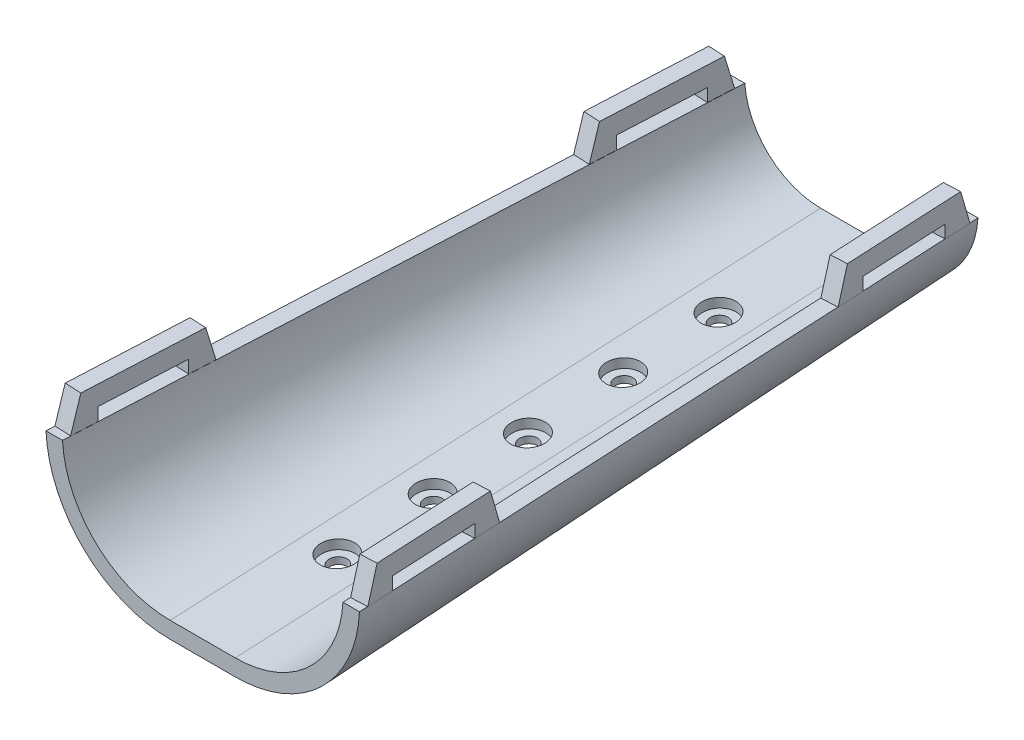
SolidWorks part; units mm, degrees
ref_plane "Front Plane" through (0, 0, 0) normal (0, 0, 1) x (1, 0, 0)
ref_plane "Top Plane" through (0, 0, 0) normal (0, 1, 0) x (1, 0, 0)
ref_plane "Right Plane" through (0, 0, 0) normal (1, 0, 0) x (0, 0, -1)
sketch "Sketch1" plane through (0, 0, 0) normal (0, 0, 1) x (1, 0, 0)
  line L0 (-7.5, 0) -> (7.5, 0)
  line L1 (-28.8, 20) -> (28.8, 20)
  line L3 (-7.5, 3.8) -> (7.5, 3.8)
  line L4 (-24.2716, 16.2) -> (24.2716, 16.2) construction
  arc A0 (7.5, 0) -> (28.8, 20) centre (7.5, 21.3423) ccw
  arc A1 (-7.5, 0) -> (-28.8, 20) centre (-7.5, 21.3423) cw
  arc A2 (7.5, 3.8) -> (24.2716, 16.2) centre (7.5, 21.3423) ccw
  arc A3 (-7.5, 3.8) -> (-24.2716, 16.2) centre (-7.5, 21.3423) cw
  arc A4 (24.2716, 16.2) -> (24.9908, 20) centre (7.5, 21.3423) ccw
  arc A5 (-24.2716, 16.2) -> (-24.9908, 20) centre (-7.5, 21.3422) cw
  point P6 (0, 0)
  dimension "D3" = 3.8
  dimension "D1" = 15
  dimension "D2" = 57.6
  dimension "D4" = 20
extrude "Boss-Extrude1" add sketch "Sketch1" along normal blind 150 draft 2.8 contours L4 A3 L3 A2 | A5 L4 A4 L1 | A3 A5 L1 A1 L0 A0 A4 A2 L3 region at (-21.6916, 6.2282, 0) region at (0, 18.1092, 0) region at (0, 10.6529, 0) draft outward yes
extrude "Cut-Extrude1" cut sketch "Sketch1<3>" along normal through all draft 2.8 contours L4 A3 L3 A2 | A5 L4 A4 L1 region at (0, 18.1092, 0) region at (0, 10.6529, 0) draft outward yes
sketch "Sketch1<3>" plane through (0, 0, 0) normal (0, 0, 1) x (1, 0, 0) same geometry as "Sketch1"
sketch "Sketch4" plane through (0, 0, 0) normal (0, 0, -1) x (-1, 0, 0)
  line L0 (43.2855, 20) -> (-43.2855, 20)
  line L1 (-43.2855, 20) -> (-43.2855, 37.75)
  line L2 (-43.2855, 37.75) -> (43.2855, 37.75)
  line L3 (43.2855, 37.75) -> (43.2855, 20)
  point P4 (0, 20)
  dimension "D1" = 17.75
  dimension "D2" = 86.571
extrude "Cut-Extrude2" cut sketch "Sketch4" against normal through all
ref_plane "Plane1" through (28.7734, 0, -1.4073) normal (0.9988, 0, -0.0488) x (-0.0488, 0, -0.9988)
sketch "Sketch5" plane through (28.7734, 0, -1.4073) normal (0.9988, 0, -0.0488) x (-0.0488, 0, -0.9988)
  line L0 (-149.5867, 20) -> (-147.3367, 27.5)
  line L1 (-1.4069, 20) -> (-151.5867, 20) construction
  line L2 (-147.3367, 27.5) -> (-119.8367, 27.5)
  line L3 (-119.8367, 27.5) -> (-117.5867, 20)
  line L4 (-117.5867, 20) -> (-123.5867, 20)
  line L5 (-123.5867, 20) -> (-123.5867, 23)
  line L6 (-123.5867, 23) -> (-143.5867, 23)
  line L7 (-143.5867, 23) -> (-143.5867, 20)
  line L8 (-143.5867, 20) -> (-149.5867, 20)
  line L9 (-76.4968, 20) -> (-76.4968, 42.8305) construction
  line L10 (-9.4069, 23) -> (-9.4069, 20)
  line L11 (-29.4069, 23) -> (-9.4069, 23)
  line L12 (-29.4069, 20) -> (-29.4069, 23)
  line L13 (-35.4069, 20) -> (-29.4069, 20)
  line L14 (-33.1569, 27.5) -> (-35.4069, 20)
  line L15 (-5.6569, 27.5) -> (-33.1569, 27.5)
  line L16 (-3.4069, 20) -> (-5.6569, 27.5)
  line L17 (-9.4069, 20) -> (-3.4069, 20)
  point P13 (-133.5867, 23)
  point P14 (-133.5867, 27.5)
  dimension "D1" = 20
  dimension "D2" = 27.5
  dimension "D3" = 6
  dimension "D4" = 7.5
  dimension "D5" = 4.5
  dimension "D6" = 2
  dimension "D7" = 41.0899
extrude "Boss-Extrude2" add sketch "Sketch5" against normal blind 3.8
ref_plane "Plane2" through (-28.7734, 0, -1.4073) normal (-0.9988, 0, -0.0488) x (-0.0488, 0, 0.9988)
sketch "Sketch6" plane through (-28.7734, 0, -1.4073) normal (-0.9988, 0, -0.0488) x (-0.0488, 0, 0.9988)
  line L0 (149.5867, 20) -> (147.3367, 27.5)
  line L1 (147.3367, 27.5) -> (119.8367, 27.5)
  line L2 (119.8367, 27.5) -> (117.5867, 20)
  line L3 (117.5867, 20) -> (123.5867, 20)
  line L4 (123.5867, 20) -> (123.5867, 23)
  line L5 (123.5867, 23) -> (143.5867, 23)
  line L6 (143.5867, 23) -> (143.5867, 20)
  line L9 (143.5867, 20) -> (149.5867, 20)
  line L10 (151.5867, 20) -> (1.4069, 20) construction
  line L11 (76.4968, 20.9106) -> (76.4968, 45.7077) construction
  line L12 (9.4069, 23) -> (9.4069, 20)
  line L13 (29.4069, 23) -> (9.4069, 23)
  line L14 (29.4069, 20) -> (29.4069, 23)
  line L15 (35.4069, 20) -> (29.4069, 20)
  line L16 (33.1569, 27.5) -> (35.4069, 20)
  line L17 (5.6569, 27.5) -> (33.1569, 27.5)
  line L18 (3.4069, 20) -> (5.6569, 27.5)
  line L19 (9.4069, 20) -> (3.4069, 20)
  point P4 (133.5867, 23)
  point P16 (133.5867, 27.5)
  point P23 (0, 0)
  dimension "D1" = 20
  dimension "D2" = 27.5
  dimension "D3" = 2
  dimension "D4" = 7.5
  dimension "D5" = 6
  dimension "D6" = 4.5
  dimension "D7" = 41.1
  dimension "D8" = 2
extrude "Boss-Extrude3" add sketch "Sketch6" against normal blind 3.8
hole_wizard "CBORE for M4 SBHCS1" positions "3DSketch1" profile "Sketch7" counterbore size "M4" standard "ANSI Metric" end condition through all
sketch3d "3DSketch1"
  line L0 (0, 3.8, 0) -> (0, -3.5362, 150) construction
  line L1 (-7.5, 3.8, 0) -> (7.5, 3.8, 0) construction
  line L2 (-7.5, -3.5362, 150) -> (7.5, -3.5362, 150) construction
  point P0 (0, -2.0175, 118.9475)
  point P2 (0, -0.9428, 96.9737)
  point P4 (0, 0.1319, 75)
  point P6 (0, 1.2066, 53.0263)
  point P8 (0, 2.2813, 31.0525)
  point P19 (0, 0, 0)
  point P20 (0, 0, 0)
  point P21 (0, 0, 0)
  point P22 (0, 0, 0)
  point P23 (0, 0, 0)
  dimension "D1" = 22
  dimension "D2" = 22
  dimension "D3" = 22
  dimension "D4" = 22
sketch "Sketch7" plane through (0, -2.0175, 118.9475) normal (1, 0, 0) x (0, -0.0488, 0.9988)
  line L0 (0, 0) -> (0, 11.1229)
  line L1 (0, 11.1229) -> (2.1, 11.1229)
  line L3 (2.1, 11.1229) -> (2.1, 2.2)
  line L4 (2.1, 2.2) -> (4, 2.2)
  line L5 (4, 2.2) -> (4, 0)
  line L7 (4, 0) -> (0, 0)
  line L11 (0, -6.35) -> (0, 107.95) construction
  dimension "Thru Hole Dia." = 4.2
  dimension "Thru Hole Depth" = 11.1229
  dimension "C'Bore Dia." = 8
  dimension "C'Bore Depth" = 2.2
